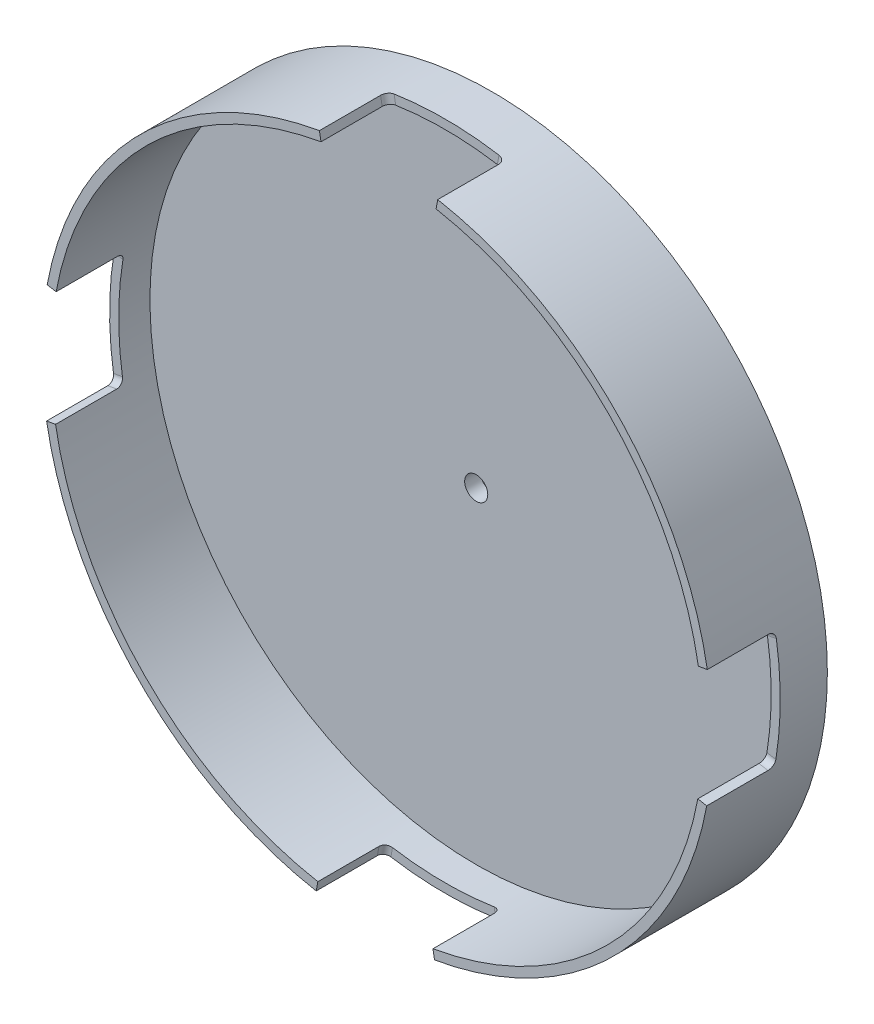
SolidWorks part; units mm, degrees
ref_plane "Front Plane" through (0, 0, 0) normal (0, 0, 1) x (1, 0, 0)
ref_plane "Top Plane" through (0, 0, 0) normal (0, 1, 0) x (1, 0, 0)
ref_plane "Right Plane" through (0, 0, 0) normal (1, 0, 0) x (0, 0, -1)
sketch "Sketch1" plane through (0, 0, 0) normal (0, 0, 1) x (1, 0, 0)
  circle A0 centre (0, 0) radius 74
  circle A1 centre (0, 0) radius 2.55
  dimension "D1" = 148
  dimension "D2" = 5.1
extrude "Boss-Extrude1" add sketch "Sketch1" along normal blind 3.5
sketch "Sketch2" plane through (0, 0, 0) normal (0, 0, 1) x (1, 0, 0)
  circle A0 centre (0, 0) radius 16
  circle A1 centre (0, 0) radius 32.5
  dimension "D1" = 65
  dimension "D2" = 32
extrude "Cut-Extrude4" cut sketch "Sketch2" along normal blind 1
fillet "Fillet1" radius 1.5 1 edges at (32.5, 0, 0)
fillet "Fillet2" radius 1.5 1 edges at (16, 0, 0)
sketch "Sketch3" plane through (0, 0, 0) normal (0, 0, 1) x (1, 0, 0)
  circle A0 centre (0, 0) radius 74
  circle A1 centre (0, 0) radius 72
  dimension "D1" = 148
  dimension "D2" = 2
extrude "Boss-Extrude2" add sketch "Sketch3" along normal blind 25.4
sketch "Sketch5" plane through (0, 0, 25.4) normal (0, 0, 1) x (1, 0, 0)
  line L0 (0, 0) -> (-12.3541, 70.9322) construction
  line L1 (-12.3541, 70.9322) -> (-12.6973, 72.9025)
  line L2 (0, 0) -> (13.0459, 70.8082) construction
  line L3 (13.0459, 70.8082) -> (13.4083, 72.7751)
  circle A0 centre (0, 0) radius 74 construction
  circle A1 centre (0, 0) radius 72 construction
  arc A2 (-12.3541, 70.9322) -> (13.0459, 70.8082) centre (0, 0) cw
  circle A3 centre (0, 0) radius 72 construction
  arc A4 (13.4083, 72.7751) -> (-12.6973, 72.9025) centre (0, 0) ccw
  dimension "D1" = 25.4
extrude "Cut-Extrude5" cut sketch "Sketch5" against normal blind 15
fillet "Fillet3" [suppressed] radius 1.5
pattern_circular "CirPattern2" count 4 over 360 about axis through (0, 0, 25.4) along (0, 0, 1) of "Cut-Extrude5"
fillet "Fillet4" radius 1.5 8 edges at (71.9174, 12.5257, 10.4) (71.7917, -13.2271, 10.4) (12.5257, -71.9174, 10.4) (-13.2271, -71.7917, 10.4) (-71.9174, -12.5257, 10.4) (-71.7917, 13.2271, 10.4) (-12.5257, 71.9174, 10.4) (13.2271, 71.7917, 10.4)
